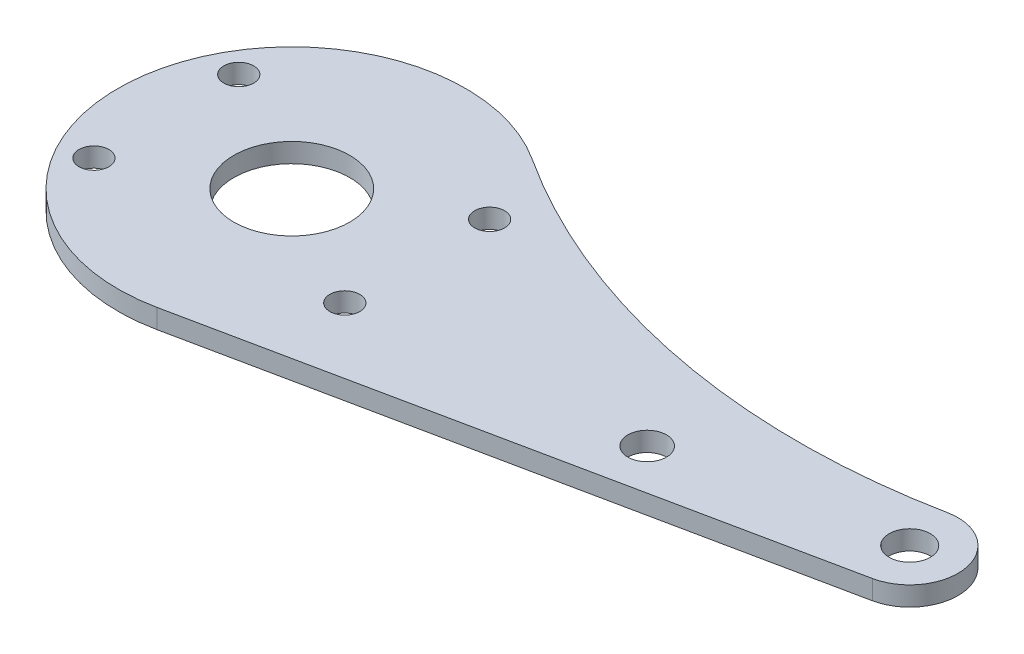
SolidWorks part; units mm, degrees
material "6061-T6 (SS)"
ref_plane "Front" through (0, 0, 0) normal (0, 0, 1) x (1, 0, 0)
ref_plane "Top" through (0, 0, 0) normal (0, 1, 0) x (1, 0, 0)
ref_plane "Right" through (0, 0, 0) normal (1, 0, 0) x (0, 0, -1)
sketch "Sketch1" plane through (0, 0, 0) normal (0, 1, 0) x (1, 0, 0)
  line L1 (5.8043, -27.9793) -> (103.2123, -7.772)
  circle A0 centre (0, 0) radius 28.575
  circle A1 centre (0, 0) radius 9.525
  circle A2 centre (101.6, 0) radius 7.9375
  circle A3 centre (101.6, 0) radius 3.3782
  arc A5 (15.5451, 23.9767) -> (100.0497, 7.7846) centre (77.7255, 119.8833) ccw
  point P8 (63.6544, 35.7878)
  point P9 (0, 0)
  point P10 (75.098, 100.7137)
  dimension "D2" = 57.15
  dimension "D3" = 15.875
  dimension "D4" = 6.7564
  dimension "D1" = 19.05
  dimension "D6" = 114.3
  dimension "D5" = 101.6
extrude "Boss-Extrude1" add sketch "Sketch1" along normal blind 3.175 contours A2 A0 | A0 | A2 A3 region at (54.0762, 0, 4.5884) region at (-27.2913, 0, -5.1166) region at (94.0416, 0, 1.5366)
sketch "Sketch4" plane through (0, 3.175, 0) normal (0, 1, 0) x (1, 0, 0)
  circle A0 centre (0, 0) radius 23.8125
  point P7 (-20.6222, 11.9062)
  point P9 (20.6222, 11.9062)
  point P11 (20.6222, -11.9062)
  point P13 (-20.6222, -11.9062)
  dimension "D1" = 47.625
  dimension "D2" = 23.8125
hole_wizard "#10 (0.1935) Diameter Hole1" positions "Sketch4" profile "Sketch3" hole size "#10" standard "ANSI Inch" end condition through all
sketch "Sketch3" plane through (-20.6222, 3.175, 11.9062) normal (1, 0, 0) x (0, 0, 1)
  line L0 (0, 0) -> (0, 3.175)
  line L1 (0, 3.175) -> (2.4574, 3.175)
  line L2 (2.4574, 3.175) -> (2.4574, 0)
  line L5 (2.4574, 0) -> (0, 0)
  line L11 (0, -6.35) -> (0, 107.95) construction
  dimension "Thru Hole Dia." = 4.9149
  dimension "Thru Hole Depth" = 3.175
sketch "Sketch7" plane through (0, 3.175, 0) normal (0, 1, 0) x (1, 0, 0)
  line L3 (65.8486, -7.4166) -> (101.6, 0) construction
  line L5 (5.8043, -27.9793) -> (103.2123, -7.772) construction
  arc A0 (103.2123, -7.772) -> (100.0497, 7.7846) centre (101.6, 0) ccw construction
  point P0 (65.8486, -7.4166)
  point P8 (109.3784, 1.5813)
  dimension "D1" = 44.45
hole_wizard "1/4 (0.25) Diameter Hole2" positions "Sketch7" profile "Sketch8" hole size "1/4" standard "ANSI Inch" end condition through all
sketch "Sketch8" plane through (65.8486, 3.175, 7.4166) normal (1, 0, 0) x (0, 0, 1)
  line L0 (0, 0) -> (0, 3.175)
  line L1 (0, 3.175) -> (3.175, 3.175)
  line L2 (3.175, 3.175) -> (3.175, 0)
  line L5 (3.175, 0) -> (0, 0)
  line L11 (0, -6.35) -> (0, 107.95) construction
  dimension "Thru Hole Dia." = 6.35
  dimension "Thru Hole Depth" = 3.175
